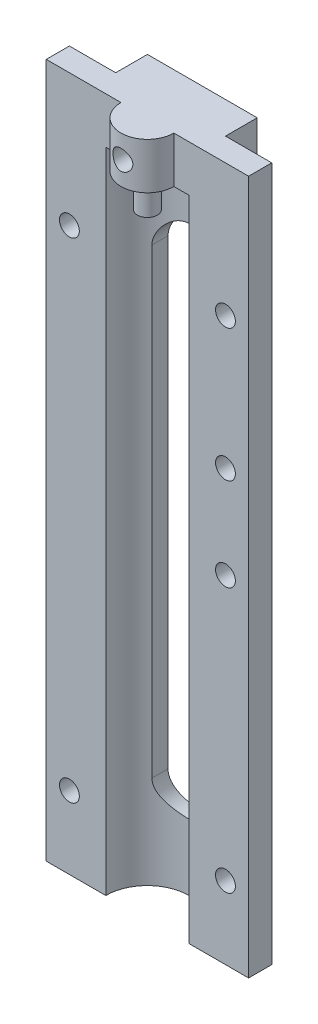
SolidWorks part; units mm, degrees
ref_plane "Front Plane" through (0, 0, 0) normal (0, 0, 1) x (1, 0, 0)
ref_plane "Top Plane" through (0, 0, 0) normal (0, 1, 0) x (1, 0, 0)
ref_plane "Right Plane" through (0, 0, 0) normal (1, 0, 0) x (0, 0, -1)
sketch "Sketch1" plane through (0, 0, 0) normal (0, 1, 0) x (1, 0, 0)
  circle A0 centre (0, 0) radius 6.3
  circle A1 centre (0, 0) radius 8.3
  dimension "D1" = 12.6
  dimension "D2" = 16.6
extrude "Boss-Extrude1" add sketch "Sketch1" along normal blind 95
sketch "Sketch3" plane through (0, 95, 0) normal (0, 1, 0) x (1, 0, 0)
  circle A1 centre (0, 0) radius 8.3
extrude "Boss-Extrude2" add sketch "Sketch3" along normal blind 3
sketch "Sketch4" plane through (0, 95, 0) normal (0, -1, 0) x (-1, 0, 0)
  circle A0 centre (0, 0) radius 1.5
  circle A1 centre (0, 0) radius 6.3
  dimension "D1" = 3
  dimension "D2" = 12.6
sketch "Sketch5" plane through (0, 98, 0) normal (0, 1, 0) x (1, 0, 0)
  line L1 (-8.3, 8.3) -> (8.3, 8.3)
  line L2 (-8.3, 8.3) -> (-8.3, -8.3)
  line L3 (-8.3, -8.3) -> (8.3, -8.3)
  line L4 (8.3, 8.3) -> (8.3, -8.3)
  line L5 (-8.3, 8.3) -> (8.3, -8.3) construction
  line L6 (-8.3, -8.3) -> (8.3, 8.3) construction
  point P0 (0, 0)
extrude "Boss-Extrude4" add sketch "Sketch5" along normal blind 7
sketch "Sketch6" plane through (0, 0, 8.3) normal (0, 0, 1) x (1, 0, 0)
  line L0 (0, 98) -> (0, 88)
  line L2 (0, 10) -> (-4.1, 10)
  line L3 (-4.1, 10) -> (-4.1, 88)
  line L4 (-4.1, 88) -> (4.1, 88)
  line L5 (4.1, 88) -> (4.1, 10)
  line L6 (4.1, 10) -> (0, 10)
  dimension "D1" = 10
  dimension "D2" = 78
  dimension "D3" = 4.1
  dimension "D4" = 8.2
extrude "Cut-Extrude1" cut sketch "Sketch6" against normal through all contours L6 L5 L4 L3 L2 region at (0, 49, 8.3)
fillet "Fillet1" radius 4.1 8 edges at (4.1, 88, -6) (4.1, 88, 6) (-4.1, 88, 6) (-4.1, 88, -6) (4.1, 10, -6) (4.1, 10, 6) (-4.1, 10, -6) (-4.1, 10, 6)
extrude "Cut-Extrude3" cut sketch "Sketch4" against normal blind 3
sketch "Sketch8" plane through (0, 95, 0) normal (0, -1, 0) x (-1, 0, 0)
  circle A0 centre (0, 0) radius 1.5
  dimension "D1" = 3
extrude "Boss-Extrude6" add sketch "Sketch8" along normal blind 2
sketch "Sketch9" plane through (-8.3, 0, 0) normal (-1, 0, 0) x (0, 0, 1)
  line L2 (0, 0) -> (3.5, 0)
  line L3 (3.5, 0) -> (3.5, 105)
  line L4 (3.5, 105) -> (-3.5, 105)
  line L5 (-3.5, 105) -> (-3.5, 0)
  line L6 (-3.5, 0) -> (0, 0)
  dimension "D1" = 3.5
  dimension "D2" = 7
extrude "Boss-Extrude7" add sketch "Sketch9" against normal up to next (2 mm away) and the other way blind 7
mirror "Mirror1" about plane through (0, 0, 0) normal (1, 0, 0) of "Boss-Extrude7"
hole_wizard "Ø3.0 (3) Diameter Hole1" positions "Sketch11" profile "Sketch12" hole size "Ø3.0" standard "ISO" end condition up to next
sketch "Sketch11" plane through (0, 0, 8.3) normal (0, 0, 1) x (1, 0, 0)
  point P0 (0, 101.5)
sketch "Sketch12" plane through (0, 101.5, 8.3) normal (1, 0, 0) x (0, -1, 0)
  line L0 (0, 0) -> (0, 16.6)
  line L1 (0, 16.6) -> (1.5, 16.6)
  line L2 (1.5, 16.6) -> (1.5, 0)
  line L5 (1.5, 0) -> (0, 0)
  line L11 (0, -6.35) -> (0, 107.95) construction
  dimension "Thru Hole Dia." = 3
  dimension "Thru Hole Depth" = 16.6
hole_wizard "Ø3.0 (3) Diameter Hole2" positions "Sketch13" profile "Sketch14" hole size "Ø3.0" standard "ISO" end condition through all
sketch "Sketch13" plane through (0, 0, 3.5) normal (0, 0, 1) x (1, 0, 0)
  line L0 (15.3, 105) -> (8.3, 105) construction
  point P0 (11.8, 85)
  point P4 (11.8, 11)
  point P11 (11.8, 105)
  dimension "D1" = 20
  dimension "D2" = 74
sketch "Sketch14" plane through (11.8, 85, 3.5) normal (1, 0, 0) x (0, -1, 0)
  line L0 (0, 0) -> (0, 11.8)
  line L1 (0, 11.8) -> (1.5, 11.8)
  line L2 (1.5, 11.8) -> (1.5, 0)
  line L5 (1.5, 0) -> (0, 0)
  line L11 (0, -6.35) -> (0, 107.95) construction
  dimension "Thru Hole Dia." = 3
  dimension "Thru Hole Depth" = 11.8
hole_wizard "Ø3.0 (3) Diameter Hole3" positions "Sketch15" profile "Sketch16" hole size "Ø3.0" standard "ISO" end condition through all
sketch "Sketch15" plane through (0, 0, -3.5) normal (0, 0, -1) x (-1, 0, 0)
  line L0 (-15.3, 105) -> (-8.3, 105) construction
  point P0 (-11.8, 65)
  point P5 (-11.8, 105)
  point P6 (-11.8, 51)
  dimension "D1" = 40
  dimension "D2" = 14
sketch "Sketch16" plane through (11.8, 65, -3.5) normal (1, 0, 0) x (0, 1, 0)
  line L0 (0, 0) -> (0, 11.8)
  line L1 (0, 11.8) -> (1.5, 11.8)
  line L2 (1.5, 11.8) -> (1.5, 0)
  line L5 (1.5, 0) -> (0, 0)
  line L11 (0, -6.35) -> (0, 107.95) construction
  dimension "Thru Hole Dia." = 3
  dimension "Thru Hole Depth" = 11.8
mirror "Mirror2" about plane through (0, 0, 0) normal (1, 0, 0) of "Ø3.0 (3) Diameter Hole2"
sketch "Sketch17" plane through (0, 0, 0) normal (0, -1, 0) x (-1, 0, 0)
  line L0 (15.3, 0) -> (4, 0)
  line L1 (15.3, 3.5) -> (15.3, -3.5) construction
  line L2 (-15.3, 0) -> (-4, 0)
  line L3 (-15.3, 3.5) -> (-15.3, -3.5) construction
  line L4 (15.3, 0) -> (15.3, -8.3)
  line L5 (15.3, -8.3) -> (-15.3, -8.3)
  line L6 (-15.3, -8.3) -> (-15.3, 8.3)
  line L7 (-15.3, 8.3) -> (15.3, 8.3)
  line L8 (15.3, 8.3) -> (15.3, 0)
  arc A0 (4, 0) -> (-4, 0) centre (0, 0) cw
  arc M6 (-7.526, -3.5) -> (7.526, -3.5) centre (0, 0) ccw
  line M7 (7.526, -3.5) -> (15.3, -3.5)
  line M8 (15.3, -3.5) -> (15.3, 3.5)
  line M12 (-15.3, 3.5) -> (-15.3, -3.5)
  line M13 (-15.3, -3.5) -> (-7.526, -3.5)
  circle M14 centre (0, 0) radius 6.3
  dimension "D1" = 4
  dimension "D2" = 4
extrude "Cut-Extrude4" cut sketch "Sketch17" against normal through all contours L2 L0 M12 M13 M6 M7 M8 M14 | L5 L4 M7 M6 | L6 L5 M6 M13 | L0 A0 L2 M14 region at (-14.9829, 0, 1.75) region at (0, 0, 6.1591) region at (-10.2031, 0, 6.1309) region at (10.2031, 0, 6.1309)
